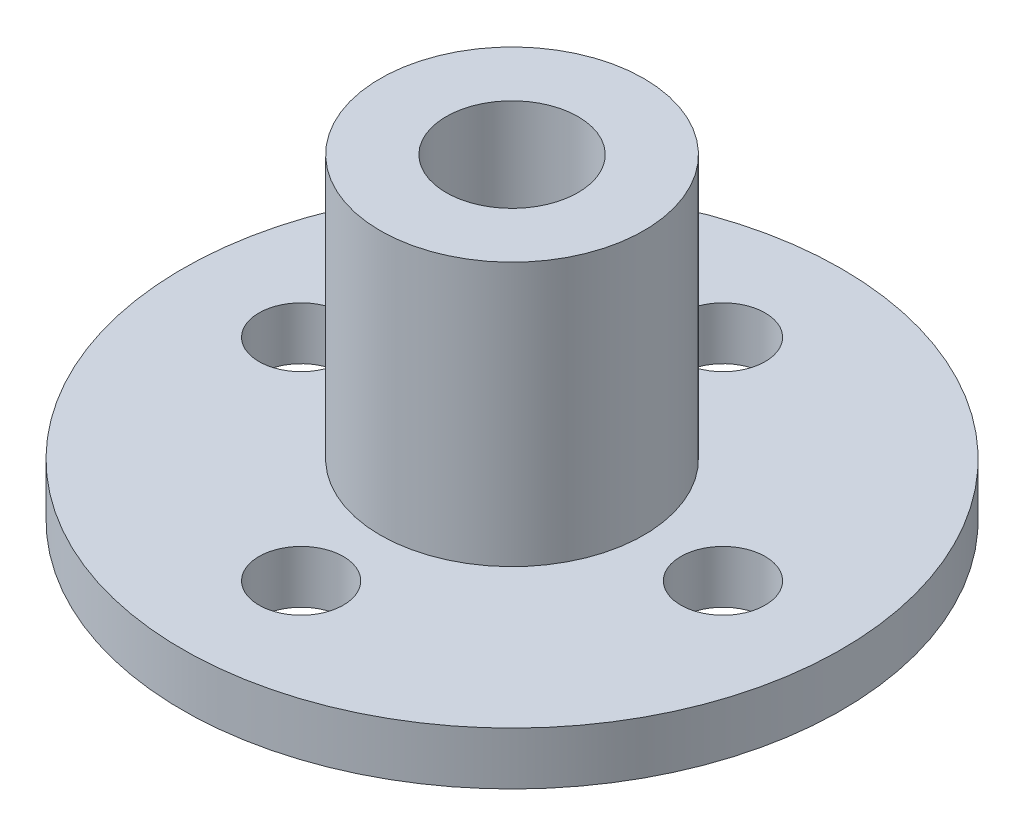
SolidWorks part; units mm, degrees
ref_plane "前视基准面" through (0, 0, 0) normal (0, 0, 1) x (1, 0, 0)
ref_plane "上视基准面" through (0, 0, 0) normal (0, 1, 0) x (1, 0, 0)
ref_plane "右视基准面" through (0, 0, 0) normal (1, 0, 0) x (0, 0, -1)
sketch "草图1" plane through (0, 0, 0) normal (0, 0, 1) x (1, 0, 0)
  line L0 (-2.5, 0.014) -> (-12.5, 0.014)
  line L1 (-12.5, 0.014) -> (-12.5, 2.014)
  line L2 (-12.5, 2.014) -> (-5, 2.014)
  line L3 (-5, 2.014) -> (-5, 12.014)
  line L4 (-5, 12.014) -> (-2.5, 12.014)
  line L5 (-2.5, 12.014) -> (-2.5, 0.014)
  line L6 (0, 0) -> (0, 12.028) construction
  dimension "D1" = 5
  dimension "D2" = 10
  dimension "D3" = 2
  dimension "D4" = 12
  dimension "D5" = 25
revolve "旋转1" add sketch "草图1" angle 360 about L6
sketch "草图2" plane through (0, 0.014, 0) normal (0, -1, 0) x (1, 0, 0)
  circle A0 centre (-8, 0) radius 1.6
  circle A1 centre (0, 0) radius 2.5 construction
  circle A2 centre (0, 8) radius 1.6
  circle A3 centre (8, 0) radius 1.6
  circle A4 centre (0, -8) radius 1.6
  point P4 (0, 0)
  point P15 (0, 0)
  dimension "D1" = 3.2
  dimension "D2" = 8
  dimension "D3" = 4
extrude "切除-拉伸1" cut sketch "草图2" against normal blind 10
ref_axis "基准轴1" through (0, 12.014, 0) along (0, -1, 0)
